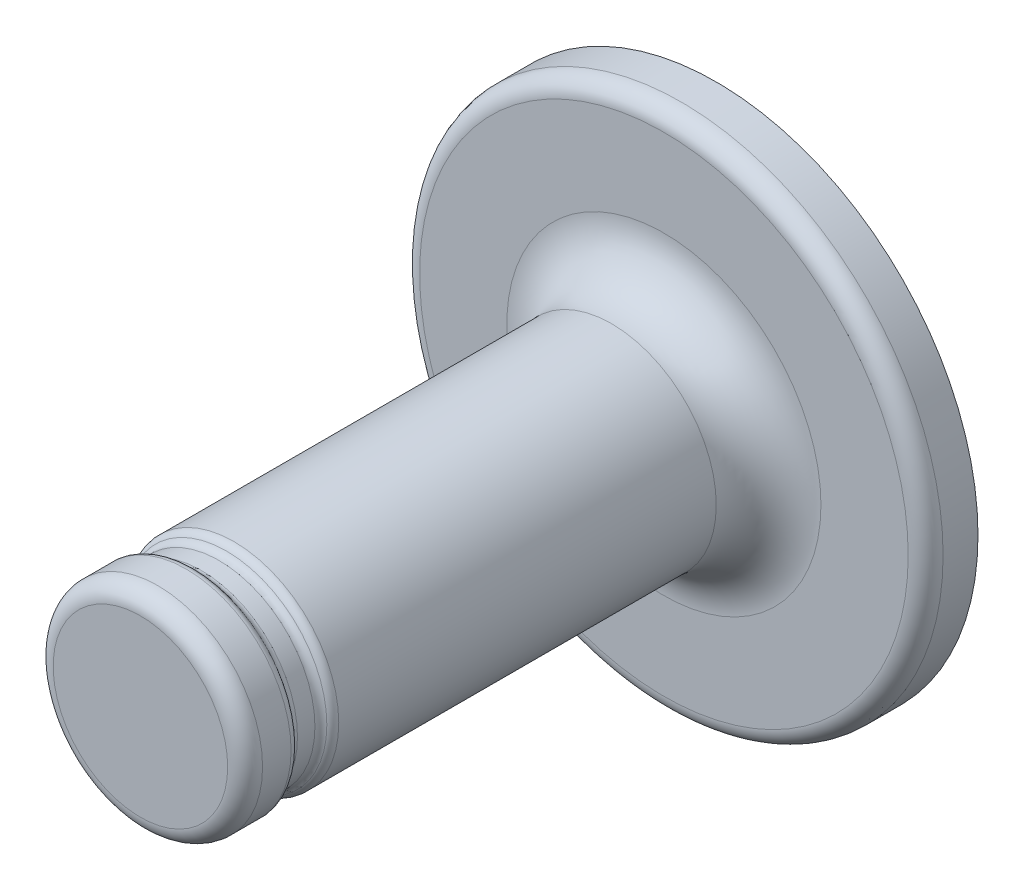
SolidWorks part; units mm, degrees
ref_plane "前视基准面" through (0, 0, 0) normal (0, 0, 1) x (1, 0, 0)
ref_plane "上视基准面" through (0, 0, 0) normal (0, 1, 0) x (1, 0, 0)
ref_plane "右视基准面" through (0, 0, 0) normal (1, 0, 0) x (0, 0, -1)
other "Configuration Table"
sketch "草图1" plane through (0, 0, 0) normal (0, 0, 1) x (1, 0, 0)
  circle A0 centre (0, 0) radius 15
  dimension "D1" = 30
extrude "凸台-拉伸1" add sketch "草图1" along normal blind 3
sketch "草图2" plane through (0, 0, 3) normal (0, 0, 1) x (1, 0, 0)
  circle A0 centre (0, 0) radius 6
  dimension "D1" = 12
extrude "凸台-拉伸2" add sketch "草图2" along normal blind 25
sketch "草图3" plane through (0, 0, 28) normal (0, 0, 1) x (1, 0, 0)
  circle A0 centre (0, 0) radius 5.5
  dimension "D1" = 11
extrude "凸台-拉伸3" add sketch "草图3" along normal blind 2
sketch "草图4" plane through (0, 0, 30) normal (0, 0, 1) x (1, 0, 0)
  circle A0 centre (0, 0) radius 6
extrude "凸台-拉伸4" add sketch "草图4" along normal blind 3
fillet "圆角1" radius 3 1 edges at (6, 0, 3)
fillet "圆角2" radius 1 1 edges at (15, 0, 3)
fillet "圆角3" radius 0.5 2 edges at (5.5, 0, 30) (5.5, 0, 28)
fillet "圆角4" radius 0.5 2 edges at (6, 0, 28) (6, 0, 30)
fillet "圆角5" radius 1 1 edges at (6, 0, 33)
